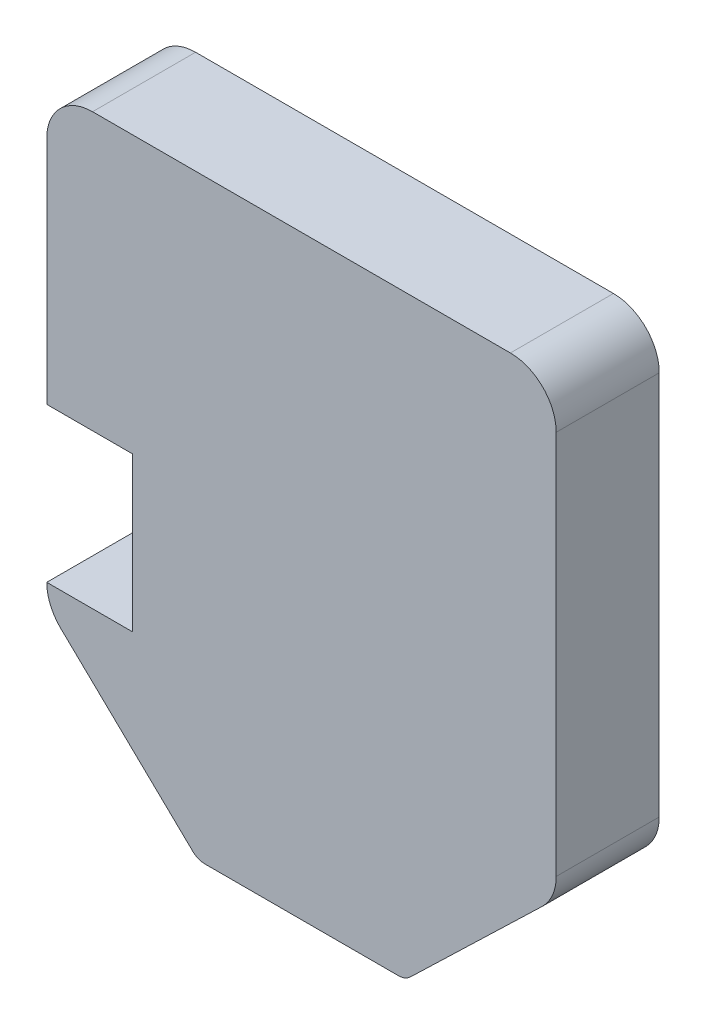
SolidWorks part; units mm, degrees
ref_plane "Front Plane" through (0, 0, 0) normal (0, 0, 1) x (1, 0, 0)
ref_plane "Top Plane" through (0, 0, 0) normal (0, 1, 0) x (1, 0, 0)
ref_plane "Right Plane" through (0, 0, 0) normal (1, 0, 0) x (0, 0, -1)
sketch "Palm_sketch" plane through (0, 0, 0) normal (0, 0, 1) x (1, 0, 0)
  line L0 (0, 78.6026) -> (0.0161, -25.3974)
  line L1 (-36.5, 78.6026) -> (36.5, 78.6026)
  line L2 (-44.5, 70.6026) -> (-44.5, 3.4047)
  line L3 (-16.8916, -25.3974) -> (16.9237, -25.3974)
  line L6 (-42.0464, -2.3605) -> (-18.9715, -24.5594)
  line L7 (42.05, -2.36) -> (19.005, -24.5581)
  line L8 (44.5, 70.6026) -> (44.5, 3.4018)
  line L9 (44.5, 70.6026) -> (44.5, 0)
  line L10 (44.5, 0) -> (19.005, -24.5581)
  arc A0 (-36.5, 78.6026) -> (-44.5, 70.6026) centre (-36.5, 70.6026) ccw
  arc A2 (36.5, 78.6026) -> (44.5, 70.6026) centre (36.5, 70.6026) cw
  arc A3 (-42.0464, -2.3605) -> (-44.5, 3.4047) centre (-36.5, 3.4047) cw
  arc A4 (42.05, -2.36) -> (44.5, 3.4018) centre (36.5, 3.4018) ccw
  arc A5 (-16.8916, -25.3974) -> (-18.9715, -24.5594) centre (-16.8916, -22.3974) cw
  arc A6 (19.005, -24.5581) -> (16.9237, -25.3974) centre (16.9237, -22.3974) cw
  dimension "D3" = 8
  dimension "D4" = 8
  dimension "D2" = 8
  dimension "D5" = 3
  dimension "D6" = 3
  dimension "D1" = 3
  dimension "D9" = 8
  dimension "D7" = 67.1978
  dimension "D8" = 33.8153
extrude "Palm_Body" add sketch "Palm_sketch" along normal mid plane 18 contours L8 A4 L7 A6 L3 A5 L6 A3 L2 A0 L1 A2
ref_axis "MCP_REFERENCE" through (36.5, 78.6026, 0) along (-1, 0, 0)
sketch "Sketch5" plane through (0, 78.6026, 0) normal (0, 1, 0) x (1, 0, 0)
  line L0 (-36.5, 0) -> (36.5, 0)
  line L1 (-36.5, -9) -> (-36.5, 9) construction
  line L2 (36.5, 0) -> (-36.5, 0) construction
  point P7 (-28, 0)
  point P8 (-28, 0)
  point P9 (-8.5, 0)
  point P10 (11, 0)
  point P11 (29, 0)
  dimension "D1" = 8.5
  dimension "D2" = 28
  dimension "D3" = 47.5
  dimension "D4" = 65.5
  dimension "D5" = 73
ref_axis "index" through (-28, 78.6026, 0) along (0, 1, 0)
ref_axis "middle" through (-8.5, 78.6026, 0) along (0, 1, 0)
ref_axis "ring" through (11, 78.6026, 0) along (0, 1, 0)
ref_axis "Little finger" through (29, 78.6026, 0) along (0, 1, 0)
sketch "Sketch6" plane through (-44.5, 0, 0) normal (-1, 0, 0) x (0, 0, 1)
  line L0 (0, 70.6026) -> (0, 3.4047)
  line L1 (9, 70.6026) -> (-9, 70.6026) construction
  line L2 (9, 3.4047) -> (-9, 3.4047) construction
  point P0 (0, 8.6026)
  dimension "D1" = 70
ref_axis "Thumb_CMC_Axis_1" through (-44.5, 8.6026, 0) along (1, 0, 0)
ref_axis "Thumb_CMC_Axis_2" through (-44.5, 8.6026, 0) along (0, 1, 0)
ref_point "wrist point"
ref_axis "Wrist_Axis" through (0.0161, -25.3974, 0) along (1, 0, 0)
ref_point "pinky"
ref_point "ring_point"
ref_point "middle_point"
ref_point "index_point"
ref_axis "index_point+right" through (-28, 78.6026, 0) along (1, 0, 0)
ref_axis "index_point+front" through (-28, 78.6026, 0) along (0, 0, 1)
ref_axis "middle+right" through (-8.5, 78.6026, 0) along (1, 0, 0)
ref_axis "middle_point+front" through (-8.5, 78.6026, 0) along (0, 0, 1)
ref_axis "ring_point+right" through (11, 78.6026, 0) along (1, 0, 0)
ref_axis "ring_point+front" through (11, 78.6026, 0) along (0, 0, 1)
ref_axis "pinky+right" through (29, 78.6026, 0) along (1, 0, 0)
ref_axis "pinky+front" through (29, 78.6026, 0) along (0, 0, 1)
ref_plane "Plane1" through (-44.5, 0, 0) normal (-1, 0, 0) x (0, 0, 1)
sketch "Sketch7" plane through (-44.5, 0, 0) normal (-1, 0, 0) x (0, 0, 1)
  line L0 (-9, 3.4047) -> (9, 3.4047)
  line L1 (9, 3.4047) -> (9, 30.3235)
  line L2 (9, 70.6026) -> (9, 3.4047) construction
  line L3 (9, 30.3235) -> (-9, 30.3235)
  line L4 (-9, 70.6026) -> (-9, 3.4047) construction
  line L5 (-9, 30.3235) -> (-9, 3.4047)
extrude "Boss-Extrude1" add sketch "Sketch7" against normal blind 15 separate body
combine bodies "Combine1" operation type subtract main body 101 bodies to subtract 102
ref_point "thumb"
ref_axis "thumv+right" through (-37, 3.4047, 0) along (1, 0, 0)
ref_axis "thumb+up" through (-37, 3.4047, 0) along (0, 1, 0)
ref_axis "thumb+front" through (-37, 3.4047, 0) along (0, 0, 1)
